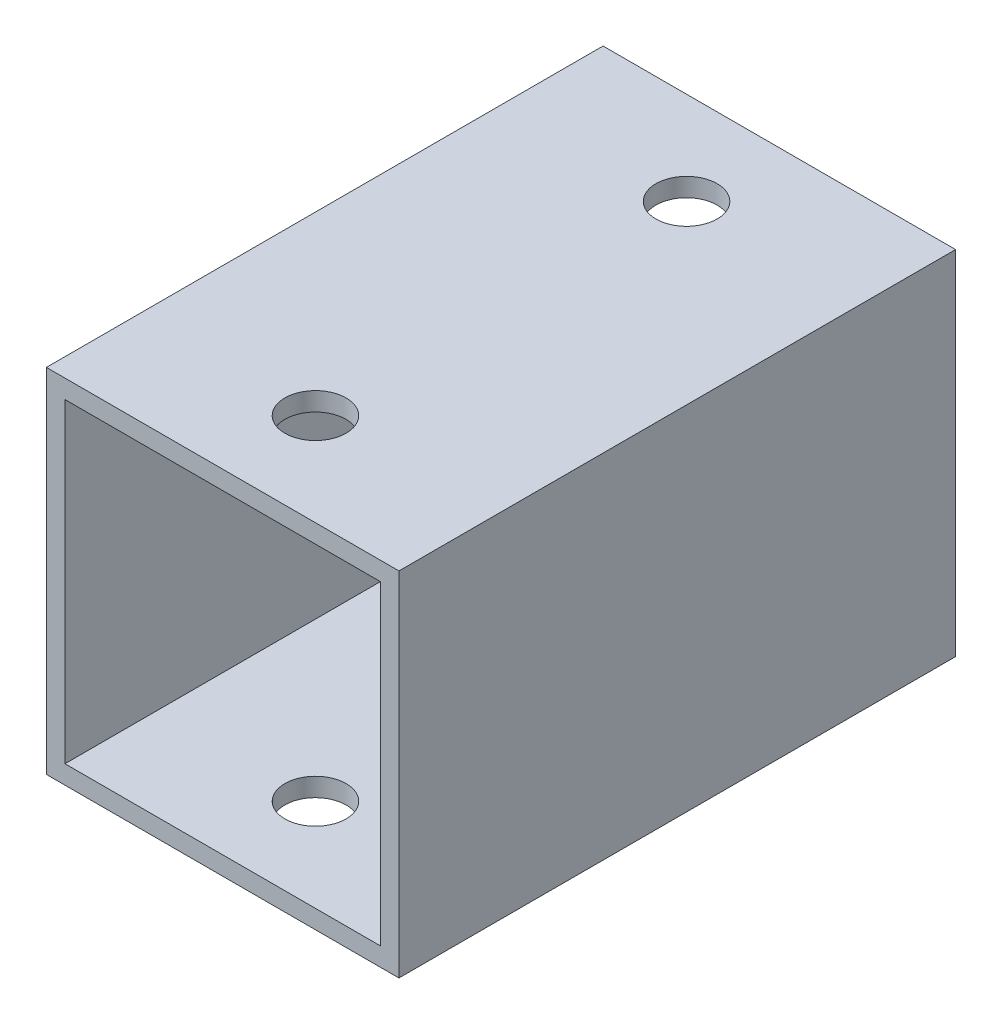
SolidWorks part; units mm, degrees
material "Gerais  - 6061-T6"
ref_plane "Plano frontal" through (0, 0, 0) normal (0, 0, 1) x (1, 0, 0)
ref_plane "Plano superior" through (0, 0, 0) normal (0, 1, 0) x (1, 0, 0)
ref_plane "Plano direito" through (0, 0, 0) normal (1, 0, 0) x (0, 0, -1)
sketch "Esboço1" plane through (0, 0, 0) normal (0, 0, 1) x (1, 0, 0)
  line L1 (0, 0) -> (19, 0)
  line L2 (0, 0) -> (0, 19)
  line L3 (0, 19) -> (19, 19)
  line L4 (19, 0) -> (19, 19)
  dimension "D1" = 19
extrude "Ressalto-extrusão1" add sketch "Esboço1" along normal blind 30
shell "Casca1" thickness 1 removed face at (9.5, 9.5, 0) removed face at (9.5, 9.5, 30)
sketch "Esboço2" plane through (0, 19, 0) normal (0, 1, 0) x (1, 0, 0)
  line L0 (19, 0) -> (0, 0) construction
  line L1 (19, -30) -> (0, -30) construction
  circle A1 centre (9.5, -25) radius 1.65
  circle A6 centre (9.5, -5) radius 1.65
  point P2 (9.5, 0)
  dimension "D1" = 3.3
  dimension "D2" = 5
  dimension "D3" = 5
extrude "Corte-extrusão1" cut sketch "Esboço2" against normal through all contours A6 | A1
